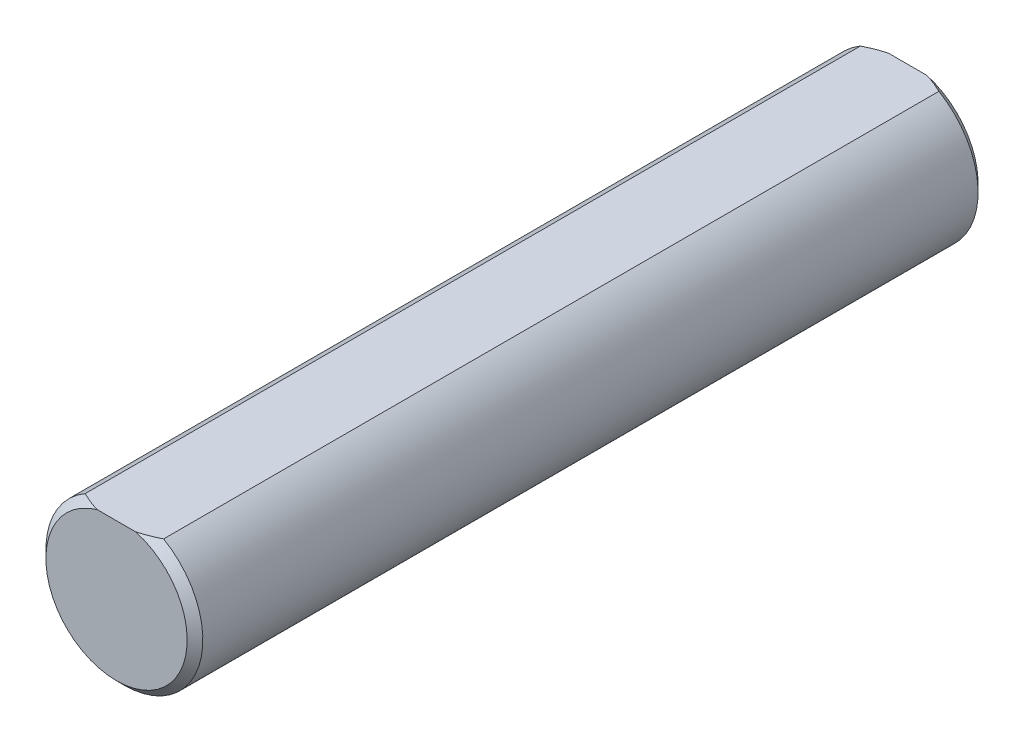
SolidWorks part; units mm, degrees
ref_plane "Front Plane" through (0, 0, 0) normal (0, 0, 1) x (1, 0, 0)
ref_plane "Top Plane" through (0, 0, 0) normal (0, 1, 0) x (1, 0, 0)
ref_plane "Right Plane" through (0, 0, 0) normal (1, 0, 0) x (0, 0, -1)
sketch "Sketch1" plane through (0, 0, 0) normal (0, 0, 1) x (1, 0, 0)
  line L0 (-1.5875, 2.7496) -> (1.5875, 2.7496) construction
  circle A1 centre (0, 0) radius 3.175 construction
  dimension "Diameter" = 6.35
  dimension "Flat Width" = 3.175
sketch "Sketch2" plane through (0, 0, 0) normal (1, 0, 0) x (0, 0, -1)
  line L0 (-16, 3.175) -> (16, 3.175) construction
  line L1 (0, 3.175) -> (0, -3.175) construction
  line L2 (0, 3.175) -> (0, -3.175) construction
  line L3 (-16, 3.175) -> (-16, -3.175) construction
  line L4 (-16, -3.175) -> (16, -3.175) construction
  point P2 (0, 3.175)
  point P3 (3.3, 3.175)
  point P4 (-3.3, 3.175)
  dimension "Length" = 32
  dimension "D2" = 12.7
  dimension "D1" = 12.7
  dimension "D-Profile Length" = 32
sketch "Sketch3" plane through (0, 0, 0) normal (0, 0, 1) x (1, 0, 0)
  circle A1 centre (0, 0) radius 3.175 construction
  circle A3 centre (0, 0) radius 3.175
extrude "Boss-Extrude2" add sketch "Sketch3" along normal up to vertex (16 mm away) and the other way up to vertex (16 mm away) up to point (0, 3.175, 16) other way up to point (0, 3.175, -16)
sketch "Sketch10" plane through (0, 0, 0) normal (0, 0, 1) x (1, 0, 0)
  line L0 (-1.5875, 2.7496) -> (1.5875, 2.7496)
  line L1 (0, 0) -> (0, 3.175) construction
  circle A0 centre (0, 0) radius 3.175 construction
  circle A1 centre (0, 0) radius 3.175 construction
  arc A2 (-1.5875, 2.7496) -> (1.5875, 2.7496) centre (0, 0) cw
extrude "Cut-Extrude5" cut sketch "Sketch10" against normal through all both and the other way through all
chamfer "Chamfer1" distance 0.3175 angle 45 2 edges at (0, -3.175, 16) (0, -3.175, -16)
equation "\"D1@Chamfer1\"= \"Diameter@Sketch1\" / 20"
equation "\"D1@Sketch2\"=\"Diameter@Sketch1\"*2"
equation "\"D2@Sketch2\"=\"D1@Sketch2\""
equation "\"D-Profile Length@Sketch2\"=\"Length@Sketch2\""
